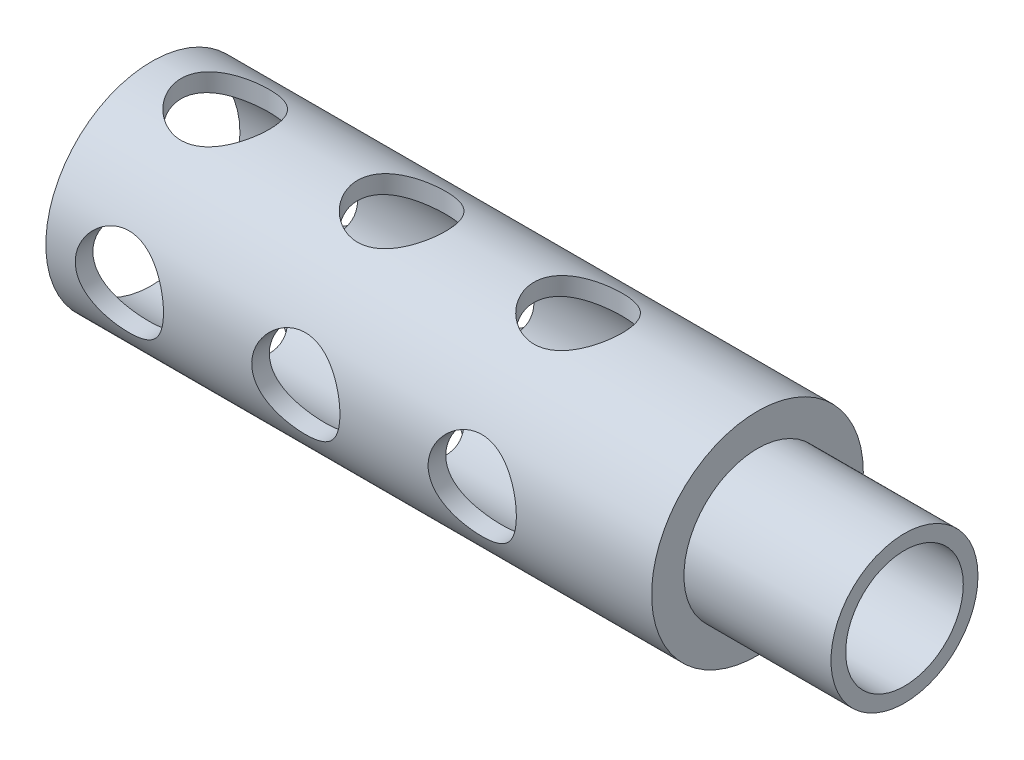
SolidWorks part; units mm, degrees
material "6061-T6 (SS)"
ref_plane "Front Plane" through (0, 0, 0) normal (0, 0, 1) x (1, 0, 0)
ref_plane "Top Plane" through (0, 0, 0) normal (0, 1, 0) x (1, 0, 0)
ref_plane "Right Plane" through (0, 0, 0) normal (1, 0, 0) x (0, 0, -1)
sketch "Sketch1" plane through (0, 0, 0) normal (1, 0, 0) x (0, 0, -1)
  circle A0 centre (0, 0) radius 11.43
  circle A1 centre (0, 0) radius 6.35
  dimension "D1" = 22.86
  dimension "D2" = 12.7
extrude "Boss-Extrude1" add sketch "Sketch1" against normal blind 81.28
sketch "Sketch5" plane through (-81.28, 0, 0) normal (-1, 0, 0) x (0, 0, 1)
  circle A0 centre (0, 0) radius 9.525
  dimension "D1" = 19.05
extrude "Cut-Extrude4" cut sketch "Sketch5" against normal blind 57.15
sketch "Sketch2" plane through (0, 0, 0) normal (1, 0, 0) x (0, 0, -1)
  circle A0 centre (0, 0) radius 7.9375
  circle A1 centre (0, 0) radius 11.43 construction
  circle A2 centre (0, 0) radius 11.43
  dimension "D1" = 15.875
extrude "Cut-Extrude1" cut sketch "Sketch2" against normal blind 15.875
ref_plane "Plane1" through (0, 25.4, 0) normal (0, 1, 0) x (-1, 0, 0)
sketch "Sketch3" plane through (0, 25.4, 0) normal (0, 1, 0) x (-1, 0, 0)
  line L0 (81.28, -11.43) -> (81.28, 11.43) construction
  line L1 (15.875, 11.43) -> (15.875, -11.43) construction
  line L2 (81.28, -11.43) -> (81.28, 11.43) construction
  line L3 (15.875, 11.43) -> (15.875, -11.43) construction
  line L4 (81.28, 0) -> (15.875, 0) construction
  circle A0 centre (73.3425, 0) radius 4.7625
  dimension "D1" = 9.525
  dimension "D2" = 7.9375
extrude "Cut-Extrude2" cut sketch "Sketch3" against normal through all
ref_axis "Axis1" through (-81.28, 0, 0) along (1, 0, 0)
pattern_linear "LPattern1" count 3 spacing 19.05 along (1, 0, 0) of "Cut-Extrude2"
ref_plane "Plane2" through (0, 0, 25.4) normal (0, 0, 1) x (1, 0, 0)
sketch "Sketch4" plane through (0, 0, 25.4) normal (0, 0, 1) x (1, 0, 0)
  line L0 (-81.28, 11.43) -> (-81.28, -11.43) construction
  line L1 (-15.875, -11.43) -> (-15.875, 11.43) construction
  line L2 (-81.28, 11.43) -> (-81.28, -11.43) construction
  line L3 (-15.875, -11.43) -> (-15.875, 11.43) construction
  line L4 (-81.28, 0) -> (-15.875, 0) construction
  circle A0 centre (-73.3425, 0) radius 4.7625
  dimension "D2" = 9.525
  dimension "D1" = 7.9375
extrude "Cut-Extrude3" cut sketch "Sketch4" against normal through all
pattern_linear "LPattern2" count 3 spacing 19.05 along (1, 0, 0) of "Cut-Extrude3"
